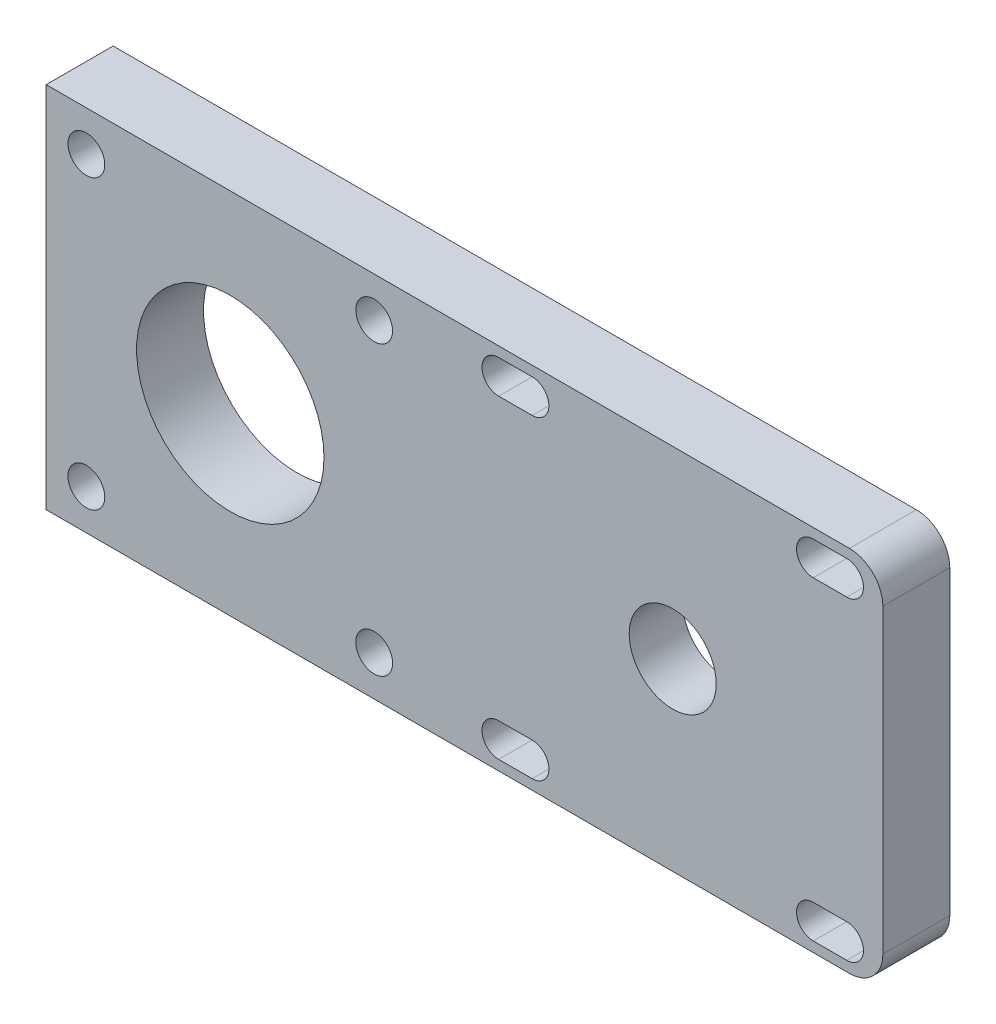
SolidWorks part; units mm, degrees
ref_plane "Piano frontale" through (0, 0, 0) normal (0, 0, 1) x (1, 0, 0)
ref_plane "Piano superiore" through (0, 0, 0) normal (0, 1, 0) x (1, 0, 0)
ref_plane "Piano destro" through (0, 0, 0) normal (1, 0, 0) x (0, 0, -1)
sketch "Schizzo1" plane through (0, 0, 0) normal (0, 0, 1) x (1, 0, 0)
  line L1 (0, 0) -> (125, 0)
  line L2 (0, 0) -> (0, 55)
  line L3 (0, 55) -> (125, 55)
  line L4 (125, 0) -> (125, 55)
  dimension "D1" = 55
  dimension "D2" = 125
extrude "Estrusione-Estrusione1" add sketch "Schizzo1" against normal blind 10
sketch "Schizzo2" plane through (0, 0, 0) normal (0, 0, 1) x (1, 0, 0)
  line L0 (0, 0) -> (0, 69.6041) construction
  line L1 (27.5, 0) -> (27.5, 69.6041) construction
  line L2 (0, 0) -> (60.1033, 0) construction
  line L3 (0, 0) -> (125, 0) construction
  line L4 (0, 27.5) -> (60.1033, 27.5) construction
  line L5 (6, 0) -> (6, 69.6041) construction
  line L6 (0, 6) -> (60.1033, 6) construction
  circle A0 centre (27.5, 27.5) radius 14
  circle A1 centre (6, 6) radius 2.75
  circle A2 centre (49, 6) radius 2.75
  circle A3 centre (49, 49) radius 2.75
  circle A4 centre (6, 49) radius 2.75
  dimension "D3" = 28
  dimension "D6" = 5.5
  dimension "D7" = 6
  dimension "D1" = 27.5
  dimension "D2" = 27.5
  dimension "D4" = 6
  dimension "D5" = 6
extrude "Taglio-Estrusione1" cut sketch "Schizzo2" against normal through all
fillet "Raccordo1" radius 5 2 edges at (125, 0, -5) (125, 55, -5)
sketch "Schizzo3" plane through (0, 0, -10) normal (0, 0, -1) x (-1, 0, 0)
  line L0 (-125, 25.5567) -> (-125, 74.1384) construction
  line L1 (-125, 5) -> (-125, 50) construction
  line L2 (-65.1, 25.5567) -> (-65.1, 74.1384) construction
  line L3 (-122.1, 25.5567) -> (-122.1, 74.1384) construction
  line L4 (-65.1, 27.5) -> (-122.1, 27.5) construction
  line L5 (-119.6, 51) -> (-114.6, 51) construction
  line L6 (-93.6, 27.5) -> (-93.6, 59.8878) construction
  line L7 (-70.1, 27.5) -> (-70.1, 63.6448) construction
  line L8 (-117.1, 27.5) -> (-117.1, 64.4221) construction
  line L9 (-65.1, 51) -> (-122.1, 51) construction
  line L10 (-65.1, 4) -> (-122.1, 4) construction
  line L11 (-117.1, 27.5) -> (-117.1, 74.1384) construction
  line L12 (-70.1, 27.5) -> (-70.1, 74.1384) construction
  line L13 (-93.6, 27.5) -> (-93.6, 74.1384) construction
  line L14 (-93.6, 55) -> (-145.2784, 55) construction
  line L15 (-120, 55) -> (0, 55) construction
  line L16 (-116.2061, 0) -> (-154.4249, 0) construction
  line L17 (0, 0) -> (-120, 0) construction
  line L18 (-119.6, 53.5) -> (-114.6, 53.5)
  line L19 (-119.6, 48.5) -> (-114.6, 48.5)
  line L20 (-67.6, 51) -> (-72.6, 51) construction
  line L21 (-67.6, 51) -> (-72.6, 51) construction
  line L22 (-67.6, 53.5) -> (-72.6, 53.5)
  line L23 (-67.6, 48.5) -> (-72.6, 48.5)
  line L24 (-119.6, 4) -> (-114.6, 4) construction
  line L25 (-119.6, 1.5) -> (-114.6, 1.5)
  line L26 (-119.6, 6.5) -> (-114.6, 6.5)
  line L27 (-67.6, 4) -> (-72.6, 4) construction
  line L28 (-67.6, 1.5) -> (-72.6, 1.5)
  line L29 (-67.6, 6.5) -> (-72.6, 6.5)
  arc A0 (-67.6, 53.5) -> (-67.6, 48.5) centre (-67.6, 51) cw
  arc A1 (-72.6, 48.5) -> (-72.6, 53.5) centre (-72.6, 51) cw
  arc A2 (-119.6, 1.5) -> (-119.6, 6.5) centre (-119.6, 4) cw
  arc A3 (-114.6, 6.5) -> (-114.6, 1.5) centre (-114.6, 4) cw
  arc A4 (-119.6, 53.5) -> (-119.6, 48.5) centre (-119.6, 51) ccw
  circle A5 centre (-93.6, 27.5) radius 6.5
  arc A6 (-114.6, 48.5) -> (-114.6, 53.5) centre (-114.6, 51) ccw
  arc A7 (-67.6, 1.5) -> (-67.6, 6.5) centre (-67.6, 4) ccw
  arc A8 (-72.6, 6.5) -> (-72.6, 1.5) centre (-72.6, 4) ccw
  point P20 (-70.1, 51)
  point P33 (-117.1, 4)
  point P45 (-117.1, 51)
  point P58 (-70.1, 4)
  dimension "D10" = 5
  dimension "D11" = 13
  dimension "D12" = 5
  dimension "D1" = 59.9
  dimension "D2" = 57
  dimension "D4" = 23.5
  dimension "D5" = 23.5
  dimension "D6" = 23.5
extrude "Taglio-Estrusione2" cut sketch "Schizzo3" against normal through all
sketch "Schizzo4" plane through (0, 0, -10) normal (0, 0, -1) x (-1, 0, 0)
  line L1 (-73.6, 9) -> (-113.6, 9)
  line L2 (-68.6, 14) -> (-68.6, 41)
  line L3 (-73.6, 46) -> (-113.6, 46)
  line L4 (-118.6, 14) -> (-118.6, 41)
  line L5 (-68.6, 9) -> (-118.6, 46) construction
  line L6 (-68.6, 46) -> (-118.6, 9) construction
  arc A0 (-73.6, 46) -> (-68.6, 41) centre (-73.6, 41) cw
  arc A1 (-68.6, 14) -> (-73.6, 9) centre (-73.6, 14) cw
  arc A2 (-113.6, 9) -> (-118.6, 14) centre (-113.6, 14) cw
  arc A3 (-118.6, 41) -> (-113.6, 46) centre (-113.6, 41) cw
  point P0 (-93.6, 27.5)
  dimension "D1" = 50
  dimension "D3" = 5
  dimension "D2" = 37
extrude "Taglio-Estrusione3" cut sketch "Schizzo4" against normal blind 2
